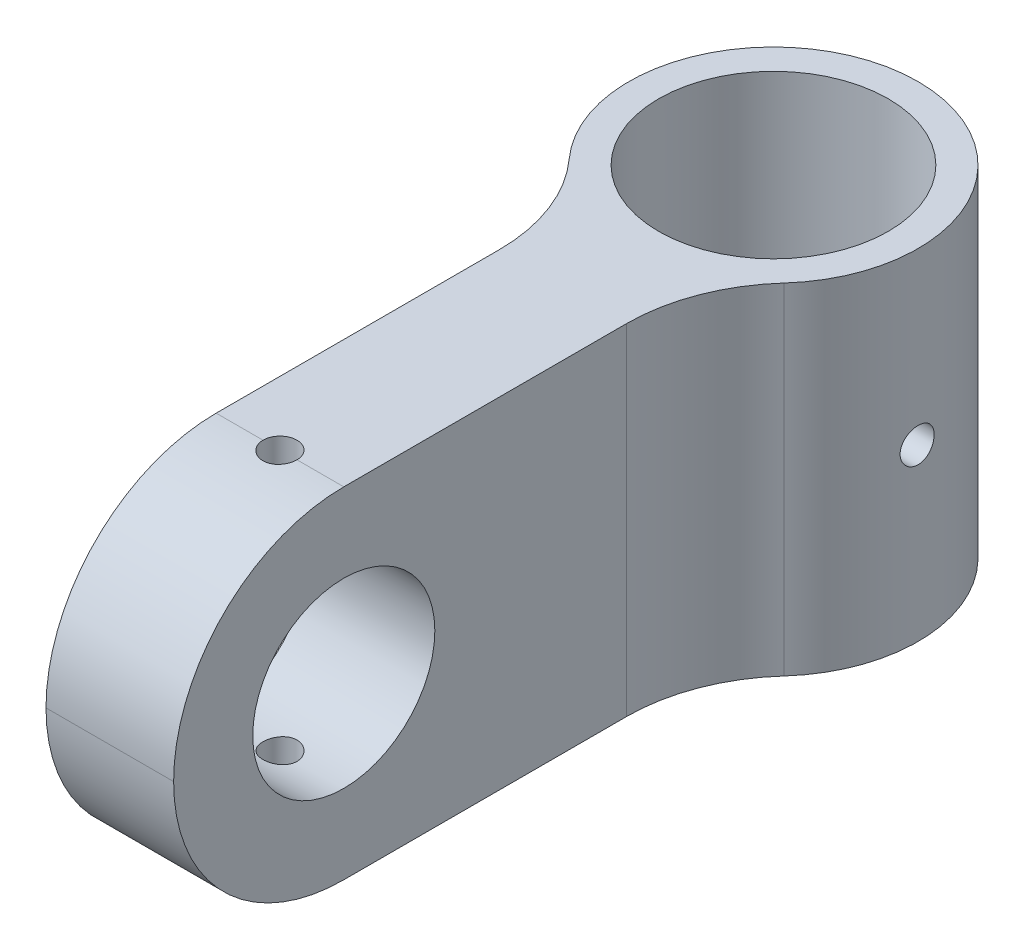
SolidWorks part; units mm, degrees
ref_plane "Front Plane" through (0, 0, 0) normal (0, 0, 1) x (1, 0, 0)
ref_plane "Top Plane" through (0, 0, 0) normal (0, 1, 0) x (1, 0, 0)
ref_plane "Right Plane" through (0, 0, 0) normal (1, 0, 0) x (0, 0, -1)
sketch "Sketch1" plane through (0, 0, 0) normal (0, 1, 0) x (1, 0, 0)
  line L0 (-55, 0) -> (55, 0) construction
  line L2 (-9.525, 79.6847) -> (-9.525, 0)
  line L3 (-9.525, 0) -> (9.525, 0)
  line L4 (9.525, 79.6847) -> (9.525, 0)
  line L5 (0, -55) -> (0, 55) construction
  arc A0 (9.525, 79.6847) -> (-9.525, 79.6847) centre (0, 99.06) ccw
  circle A1 centre (0, 99.06) radius 17.145
  circle A2 centre (0, 25.4) radius 2.54
  dimension "D3" = 25.4
  dimension "D4" = 21.59
  dimension "D5" = 34.29
  dimension "D1" = 99.06
  dimension "D2" = 9.525
  dimension "D6" = 19.05
extrude "Boss-Extrude1" add sketch "Sketch1" along normal mid plane 50.8
sketch "Sketch2" plane through (9.525, 0, 0) normal (1, 0, 0) x (0, 0, -1)
  line L0 (55, 0) -> (-55, 0) construction
  line L1 (0, 55) -> (0, -55) construction
  line L2 (99.06, 25.4) -> (99.06, -25.4) construction
  circle A0 centre (25.4, 0) radius 13.589
  circle A1 centre (99.06, 0) radius 2.54
  dimension "D1" = 25.4
  dimension "D2" = 0
  dimension "D3" = 27.178
extrude "Cut-Extrude1" cut sketch "Sketch2" against normal through all both and the other way through all
fillet "Fillet1" radius 25.4 2 edges at (0, -25.4, 0) (0, 25.4, 0)
fillet "Fillet2" radius 25.4 2 edges at (-9.525, 0, -79.6847) (9.525, 0, -79.6847)
